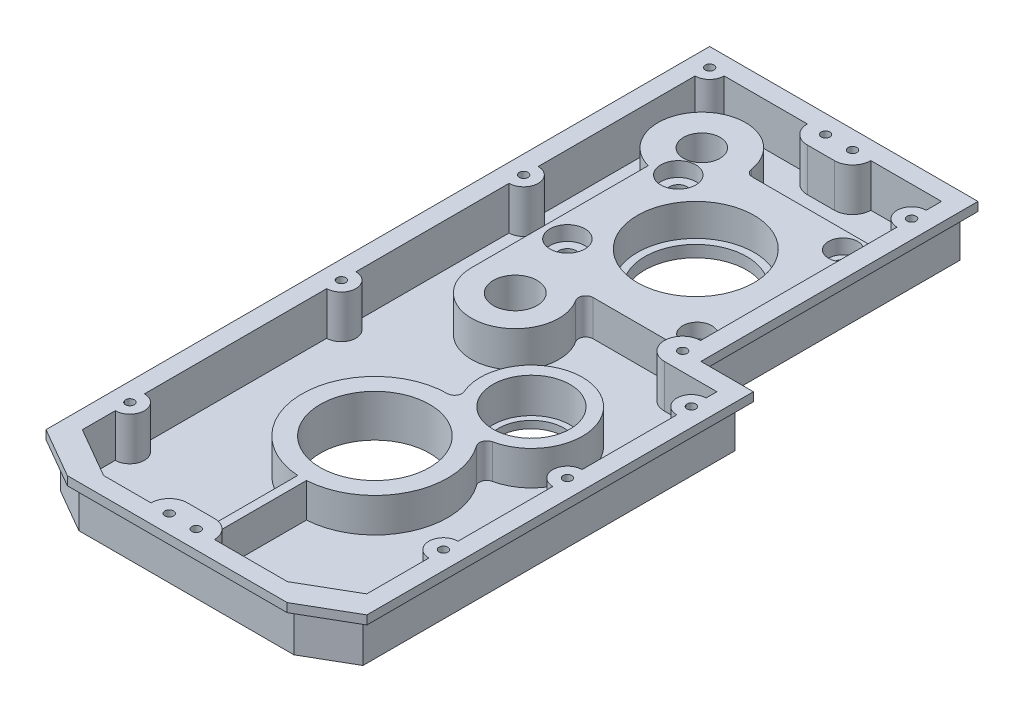
SolidWorks part; units mm, degrees
note: The reader was unsure of these and kept them because the rebuilt part matched: shared geometry of "Sketch1<6>", "Sketch1<7>", "Sketch1<8>", "Sketch1<10>", "Sketch1<11>", "Sketch1<13>", "Sketch1<15>", "Sketch1<16>", "Sketch1<17>".
ref_plane "Front Plane" through (0, 0, 0) normal (0, 0, 1) x (1, 0, 0)
ref_plane "Top Plane" through (0, 0, 0) normal (0, 1, 0) x (1, 0, 0)
ref_plane "Right Plane" through (0, 0, 0) normal (1, 0, 0) x (0, 0, -1)
sketch "Sketch1" plane through (0, 0, 0) normal (0, 1, 0) x (1, 0, 0)
  line L12 (0, 0) -> (55.5013, 0) construction
  line L13 (61, 107.5) -> (-98, 107.5)
  line L14 (-98, 107.5) -> (-98, -322.587)
  line L15 (-63.5096, -342.5) -> (62.5096, -342.5)
  line L16 (97, -322.587) -> (97, -82.5)
  line L17 (97, -82.5) -> (61, -82.5)
  line L18 (61, -82.5) -> (61, -66.7678)
  line L19 (-110.5, 120) -> (-110.5, -335)
  line L20 (-75.859, -355) -> (74.859, -355)
  line L21 (109.5, -335) -> (109.5, -70)
  line L22 (109.5, -70) -> (73.5, -70)
  line L23 (73.5, -70) -> (73.5, 120)
  line L24 (73.5, 120) -> (-110.5, 120)
  line L25 (74.859, -355) -> (109.5, -335)
  line L26 (62.5096, -342.5) -> (97, -322.587)
  line L27 (66.359, -340.2776) -> (101, -320.2776) construction
  line L28 (97, -342.5) -> (97, -82.5) construction
  line L29 (-98, -342.5) -> (97, -342.5) construction
  line L30 (109.5, -355) -> (109.5, -70) construction
  line L31 (-110.5, -355) -> (109.5, -355) construction
  line L32 (-75.859, -355) -> (-110.5, -335)
  line L33 (-63.5096, -342.5) -> (-98, -322.587)
  line L34 (-67.359, -340.2776) -> (-102, -320.2776) construction
  line L35 (-98, 107.5) -> (-98, -342.5) construction
  line L36 (-110.5, 120) -> (-110.5, -355) construction
  line L37 (50.1589, -64) -> (-6.3961, -64)
  line L38 (-65.79, -88) -> (-65.79, 33.1691)
  line L39 (61, 62.14) -> (-23.359, 62.14)
  line L40 (0, 95) -> (-18.5, 95)
  line L41 (-3, -269.9099) -> (-3, -342.5)
  line L42 (3, -269.9099) -> (3, -342.5)
  line L43 (0, 0) -> (0, -342.5) construction
  line L44 (-18.5, -330) -> (0, -330)
  line L45 (-74.1843, -348.75) -> (73.1843, -348.75)
  line L46 (73.1843, -348.75) -> (103.25, -331.3916)
  line L47 (103.25, -331.3916) -> (103.25, -76.25)
  line L48 (103.25, -76.25) -> (67.25, -76.25)
  line L49 (67.25, -76.25) -> (67.25, 113.75)
  line L50 (67.25, 113.75) -> (-104.25, 113.75)
  line L51 (-104.25, 113.75) -> (-104.25, -331.3916)
  line L52 (-74.1843, -348.75) -> (-104.25, -331.3916)
  line L53 (61, -66.7678) -> (61, 107.5)
  line L54 (61, -82.5) -> (61, 107.5) construction
  circle A0 centre (0, 0) radius 40
  circle A1 centre (0, 0) radius 35
  circle A2 centre (-98, 107.5) radius 3
  circle A3 centre (-98, 107.5) radius 10
  circle A4 centre (-98, -20) radius 3
  circle A5 centre (-98, -20) radius 10
  circle A6 centre (-98, -145) radius 3
  circle A7 centre (-98, -145) radius 10
  circle A8 centre (-98, -290) radius 3
  circle A9 centre (-98, -290) radius 10
  circle A10 centre (97, -270) radius 3
  circle A11 centre (97, -270) radius 10
  circle A12 centre (97, -185) radius 3
  circle A13 centre (97, -185) radius 10
  circle A14 centre (97, -100) radius 3
  circle A15 centre (97, -100) radius 10
  circle A18 centre (51, -50) radius 6
  circle A19 centre (51, -50) radius 10
  circle A20 centre (-35.79, -88) radius 15
  arc A21 (-65.79, -88) -> (-10.5952, -71.7143) centre (-35.79, -88) ccw
  arc A22 (-6.3961, -64) -> (-10.5952, -71.7143) centre (-6.3961, -69) ccw
  circle A23 centre (-58, 62.14) radius 12.5
  arc A24 (-28.3077, 66.4257) -> (-65.79, 33.1691) centre (-58, 62.14) ccw
  circle A25 centre (51, 50) radius 6
  circle A26 centre (51, 50) radius 10
  arc A28 (-28.3077, 66.4257) -> (-23.359, 62.14) centre (-23.359, 67.14) ccw
  circle A29 centre (-50, 38) radius 6
  circle A30 centre (-50, 38) radius 12
  circle A31 centre (-50, -38) radius 12
  circle A32 centre (-50, -38) radius 6
  circle A33 centre (0, 107.5) radius 3
  circle A34 centre (-18.5, 107.5) radius 3
  arc A35 (12.5, 107.5) -> (0, 95) centre (0, 107.5) cw
  arc A36 (-18.5, 95) -> (-31, 107.5) centre (-18.5, 107.5) cw
  circle A37 centre (61, 87) radius 3
  circle A38 centre (61, 87) radius 10
  circle A39 centre (0, -220) radius 37.5
  arc A40 (-0.3092, -170.001) -> (40.7252, -190.9921) centre (0, -220) ccw
  circle A41 centre (36.32, -149) radius 22.5
  circle A42 centre (36.32, -149) radius 26.5
  arc A43 (43.738, -183.2049) -> (4.2424, -163.0009) centre (36.32, -149) ccw
  arc A44 (4.2424, -163.0009) -> (-0.3092, -170.001) centre (-0.3401, -165.0011) cw
  arc A45 (43.738, -183.2049) -> (40.7252, -190.9921) centre (44.7977, -188.0913) ccw
  circle A46 centre (0, -342.5) radius 3
  circle A47 centre (-18.5, -342.5) radius 3
  arc A48 (-31, -342.5) -> (-18.5, -330) centre (-18.5, -342.5) cw
  arc A49 (0, -330) -> (12.5, -342.5) centre (0, -342.5) cw
  circle A54 centre (61, -70) radius 3
  arc A55 (61, -82.5) -> (50.1589, -64) centre (61, -70.0735) cw
  arc A56 (50.1589, -64) -> (61, -57.6471) centre (61, -70.0735) cw
  dimension "D1" = 80
  dimension "D2" = 70
  dimension "D7" = 61
  dimension "D8" = 70
  dimension "D9" = 12.5
  dimension "D10" = 6
  dimension "D11" = 20
  dimension "D12" = 20
  dimension "D13" = 145
  dimension "D14" = 290
  dimension "D15" = 30
  dimension "D16" = 270
  dimension "D17" = 65
  dimension "D18" = 17
  dimension "D19" = 30
  dimension "D20" = 17
  dimension "D21" = 185
  dimension "D22" = 100
  dimension "D23" = 12
  dimension "D24" = 20
  dimension "D25" = 50
  dimension "D26" = 64
  dimension "D27" = 88
  dimension "D28" = 30
  dimension "D29" = 60
  dimension "D30" = 35.79
  dimension "D31" = 10
  dimension "D33" = 25
  dimension "D34" = 62.14
  dimension "D3" = 97
  dimension "D4" = 98
  dimension "D5" = 342.5
  dimension "D6" = 107.5
  dimension "D32" = 60
  dimension "D35" = 58
  dimension "D36" = 24
  dimension "D37" = 12
  dimension "D38" = 50
  dimension "D39" = 38
  dimension "D40" = 18.5
  dimension "D41" = 12.5
  dimension "D42" = 0
  dimension "D43" = 33
  dimension "D44" = 100
  dimension "D45" = 220
  dimension "D47" = 70
  dimension "D48" = 53
  dimension "D49" = 45
  dimension "D50" = 5
  dimension "D51" = 149
  dimension "D52" = 75
  dimension "D54" = 18.5
  dimension "D55" = 12.5
  dimension "D56" = 6.25
  dimension "D57" = 46.8615
  dimension "D58" = 10.8411
  dimension "D46" = 36.32
  dimension "D53" = 6
extrude "Boss-Extrude1" add sketch "Sketch1" against normal blind 35
extrude "Cut-Extrude1" cut sketch "Sketch1<6>" against normal blind 5
sketch "Sketch1<6>" plane through (0, 0, 0) normal (0, 1, 0) x (1, 0, 0) same geometry as "Sketch1"
extrude "Cut-Extrude2" cut sketch "Sketch1<7>" against normal through all contours A20
sketch "Sketch1<7>" plane through (0, 0, 0) normal (0, 1, 0) x (1, 0, 0) same geometry as "Sketch1"
extrude "Cut-Extrude3" cut sketch "Sketch1<8>" against normal blind 27 contours A0 A1
sketch "Sketch1<8>" plane through (0, 0, 0) normal (0, 1, 0) x (1, 0, 0) same geometry as "Sketch1"
extrude "Boss-Extrude2" add sketch "Sketch1<10>" against normal up to surface (25 mm away) from offset 10 offset against normal yes
sketch "Sketch1<10>" plane through (0, 0, 0) normal (0, 1, 0) x (1, 0, 0) same geometry as "Sketch1"
extrude "Cut-Extrude4" cut sketch "Sketch1<11>" against normal blind 15 contours A19 A18 | A26 A25 | A30 A29 | A31 A32
sketch "Sketch1<11>" plane through (0, 0, 0) normal (0, 1, 0) x (1, 0, 0) same geometry as "Sketch1"
extrude "Cut-Extrude6" cut sketch "Sketch1<13>" against normal blind 29.5
sketch "Sketch1<13>" plane through (0, 0, 0) normal (0, 1, 0) x (1, 0, 0) same geometry as "Sketch1"
extrude "Boss-Extrude3" add sketch "Sketch1<15>" against normal up to surface (5 mm away) from offset 30 contours A42 A41 up to face at (-50, -35, 44) offset against normal yes
sketch "Sketch1<15>" plane through (0, 0, 0) normal (0, 1, 0) x (1, 0, 0) same geometry as "Sketch1"
extrude "Cut-Extrude7" cut sketch "Sketch1<16>" against normal blind 6 contours A45 A43 A44 A40 A42 A39 | L44 A49 L42 A40 L41
sketch "Sketch1<16>" plane through (0, 0, 0) normal (0, 1, 0) x (1, 0, 0) same geometry as "Sketch1"
extrude "Cut-Extrude8" cut sketch "Sketch1<17>" against normal up to surface (10 mm away) contours L16 A14 | L16 A14 | L16 A12 | L16 A10 | L18 A54 | L18 A54 up to face at (-98, -10, -104.5)
sketch "Sketch1<17>" plane through (0, 0, 0) normal (0, 1, 0) x (1, 0, 0) same geometry as "Sketch1"
sketch "Sketch2" plane through (0, 0, 0) normal (0, 1, 0) x (1, 0, 0)
  line L0 (-104.25, 113.75) -> (-104.25, -331.3916) construction
  line L1 (-74.1843, -348.75) -> (-104.25, -331.3916) construction
  line L2 (-74.1843, -348.75) -> (73.1843, -348.75) construction
  line L3 (73.1843, -348.75) -> (103.25, -331.3916) construction
  line L4 (103.25, -331.3916) -> (103.25, -76.25) construction
  line L5 (103.25, -76.25) -> (67.25, -76.25) construction
  line L6 (67.25, -76.25) -> (67.25, 113.75) construction
  line L7 (67.25, 113.75) -> (-104.25, 113.75) construction
  line L8 (-104.25, 113.75) -> (-104.25, -331.3916)
  line L9 (-74.1843, -348.75) -> (-104.25, -331.3916)
  line L10 (-74.1843, -348.75) -> (73.1843, -348.75)
  line L11 (73.1843, -348.75) -> (103.25, -331.3916)
  line L12 (103.25, -331.3916) -> (103.25, -76.25)
  line L13 (103.25, -76.25) -> (67.25, -76.25)
  line L14 (67.25, -76.25) -> (67.25, 113.75)
  line L15 (67.25, 113.75) -> (-104.25, 113.75)
extrude "Cut-Extrude9" cut sketch "Sketch2" against normal through all from offset 6 flip side to cut
